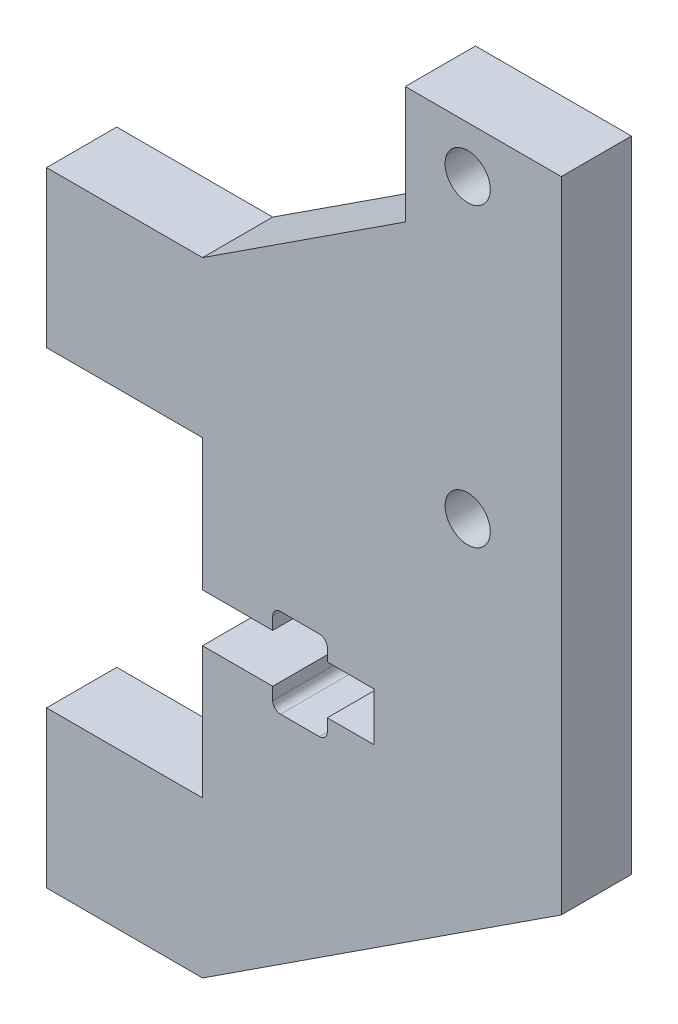
SolidWorks part; units mm, degrees
ref_plane "Front Plane" through (0, 0, 0) normal (0, 0, 1) x (1, 0, 0)
ref_plane "Top Plane" through (0, 0, 0) normal (0, 1, 0) x (1, 0, 0)
ref_plane "Right Plane" through (0, 0, 0) normal (1, 0, 0) x (0, 0, -1)
sketch "Sketch1" plane through (0, 0, 0) normal (0, 0, 1) x (1, 0, 0)
  line L0 (13, 3.4783) -> (0, -5)
  line L1 (0, -5) -> (-10, -5)
  line L2 (-10, -5) -> (-10, -15)
  line L3 (-10, -15) -> (0, -15)
  line L4 (0, -15) -> (0, -35)
  line L5 (0, -35) -> (-10, -35)
  line L6 (-10, -35) -> (-10, -45)
  line L7 (-10, -45) -> (0, -45)
  line L10 (0, -45) -> (23, -30)
  line L11 (23, -30) -> (23, 11)
  line L12 (23, 11) -> (13, 11)
  line L13 (13, 11) -> (13, 3.4783)
  line L15 (0, -5) -> (0, -45) construction
  line L16 (-10, -10) -> (0, -10) construction
  line L17 (-10, -40) -> (0, -40) construction
  line L18 (-10, -15) -> (-10, -35) construction
  line L19 (-10, -25) -> (0, -25) construction
  dimension "D1" = 10
  dimension "D2" = 10
  dimension "D3" = 10
  dimension "D4" = 10
  dimension "D5" = 15
  dimension "D8" = 10
  dimension "D10" = 13
  dimension "D6" = 15
  dimension "D7" = 16
extrude "Boss-Extrude1" add sketch "Sketch1" along normal blind 4.5
sketch "Sketch2" plane through (0, 0, 4.5) normal (0, 0, 1) x (1, 0, 0)
  line L0 (0, -25) -> (23, -25) construction
  line L1 (0, -15) -> (0, -35) construction
  line L3 (11, -26.55) -> (11, -23.45) construction
  line L4 (11, -23.45) -> (0, -23.45) construction
  line L5 (0, -26.55) -> (0, -23.45)
  line L6 (0, -23.45) -> (4.5, -23.45)
  line L7 (4.5, -23.45) -> (4.5, -22.65)
  line L8 (5, -22.15) -> (7.5, -22.15)
  line L9 (8, -22.65) -> (8, -23.45)
  line L10 (8, -23.45) -> (11, -23.45)
  line L11 (11, -23.45) -> (11, -26.55)
  line L12 (11, -26.55) -> (0, -26.55) construction
  line L13 (8, -26.55) -> (11, -26.55)
  line L14 (8, -27.35) -> (8, -26.55)
  line L15 (5, -27.85) -> (7.5, -27.85)
  line L16 (4.5, -26.55) -> (4.5, -27.35)
  line L17 (0, -26.55) -> (4.5, -26.55)
  line L18 (23, -30) -> (23, 11) construction
  arc A0 (7.5, -22.15) -> (8, -22.65) centre (7.5, -22.65) cw
  arc A1 (4.5, -22.65) -> (5, -22.15) centre (5, -22.65) cw
  arc A2 (4.5, -27.35) -> (5, -27.85) centre (5, -27.35) ccw
  arc A3 (7.5, -27.85) -> (8, -27.35) centre (7.5, -27.35) ccw
  point P15 (8, -22.15)
  point P18 (4.5, -22.15)
  point P27 (11, -25)
  point P29 (4.5, -27.85)
  point P30 (8, -27.85)
  dimension "D6" = 0.5
  dimension "D1" = 11
  dimension "D2" = 1.55
  dimension "D3" = 8
  dimension "D4" = 3.5
  dimension "D5" = 2.85
extrude "screw-cutout" cut sketch "Sketch2" against normal through all
sketch "Sketch3" plane through (0, 0, 4.5) normal (0, 0, 1) x (1, 0, 0)
  line L0 (17, 55) -> (17, -45) construction
  line L3 (13, 11) -> (13, 3.4783) construction
  line L5 (-10, -45) -> (0, -45) construction
  line L10 (11, -26.55) -> (11, -23.45) construction
  circle A1 centre (17, 8) radius 1.45
  circle A5 centre (17, -11) radius 1.45
  point P8 (11, -25)
  dimension "D4" = 2.9
  dimension "D11" = 2.9
  dimension "D6" = 4
  dimension "D12" = 19
  dimension "D2" = 14
extrude "Cut-Extrude2" cut sketch "Sketch3" against normal through all
sketch "Sketch4" [suppressed] plane through (0, 0, 4.5) normal (0, 0, 1) x (1, 0, 0)
  line L0 (17, -11) -> (17, 8) construction
  line L1 (17, -1.5) -> (13, -1.5) construction
  line L2 (13, 11) -> (13, 3.4783) construction
  line L4 (15, 2.5) -> (13, 2.5)
  line L5 (15, 2.5) -> (15, -5.5)
  line L6 (15, -5.5) -> (13, -5.5)
  line L7 (13, 2.5) -> (13, -5.5)
  line L8 (15, 2.5) -> (13, -5.5) construction
  line L9 (15, -5.5) -> (13, 2.5) construction
  circle A1 centre (17, 8) radius 1.55 construction
  circle A3 centre (17, -11) radius 1.55 construction
  point P11 (14, -1.5)
  dimension "D1" = 8
  dimension "D2" = 2
  dimension "D3" = 3
equation "\"X-ROD-SPACING\"=45"
equation "\"Y-ROD-SPACING\"=75"
equation "\"Z-ROD-SPACING\"=17.5"
equation "\"Y-BED-OFFSET\"=2"
equation "\"Y-BED-ROD-INSET\"=3.5"
equation "\"T-SLOT-NUT-FILLET-RADIUS\"=0.5"
equation "\"T-SLOT-SCREW-SHAFT-RADIUS\"=1.55"
equation "\"T-SLOT-SCREW-SHAFT-CUTOUT-LENGTH\"=11.0"
equation "\"T-SLOT-NUT-DEPTH\"=3.5"
equation "\"T-SLOT-NUT-WIDTH\"=2.85"
equation "\"T-SLOT-NUT-END-DISTANCE\"=8"
equation "\"ACRYLIC-THICKNESS\"=10"
equation "\"ACRYLIC-THICKNESS2\"=4.5"
equation "\"ACRYLIC-TAB-CUTOUT-SIZE\"=\"ACRYLIC-THICKNESS\"+\"ACRYLIC-TAB-TOLERANCE\"*2"
equation "\"ACRYLIC-TAB-WIDTH\"=\"ACRYLIC-THICKNESS\""
equation "\"ACRYLIC-M3-HOLE\"=2.9"
equation "\"SMOOTHROD-CAP-SCREW-DISTANCE\"=20"
equation "\"FRAME-WIDTH-INNER\"=370"
equation "\"NEMA17-HOLE-SPACING\"=31"
equation "\"NEMA17-CENTRAL-CUTOUT\"=22.5"
equation "\"Z-BRACKET-REACH\"=55"
equation "\"Z-ROD-INSET\"=16"
equation "\"TOP-BRACKET-SPACING\"=40"
equation "\"SMOOTHROD-X-LENGTH\"=350"
equation "\"SMOOTHROD-Y-LENGTH\"=350"
equation "\"SMOOTHROD-Z-LENGTH\"=350"
equation "\"SMOOTHROD-TIGHTENING-HEADROOM\"=.25"
equation "\"LEADSCREW-Z-LENGTH\"=300"
equation "\"SCREW-LENGTH-FRAME\"=\"ACRYLIC-THICKNESS\" + 10"
equation "\"SCREW-HEAD-RADIUS\"=6"
equation "\"PRINTED-X-SMOOTHROD-DIAMETER\"=8.4"
equation "\"PRINTED-X-SMOOTHROD-CUTOUT\"=10"
equation "\"PRINTED-X-BASE-HEIGHT\"=10"
equation "\"PRINTED-LM8UU-CUTOUT-SIZE\"=15.5"
equation "\"PRINTED-LM8UU-CUTOUT-LENGTH\"=24.5"
equation "\"PRINTED-X-IDLER-HEIGHT\"=16"
equation "\"PSU-MOUNTING-WIDTH\"=95"
equation "\"PSU-MOUNTING-HEIGHT\"=177"
equation "\"Y-BELT-TO-ROD-DISTANCE\"=20"
equation "\"SPOOL-HOLDER-ROD-SPACING\"=150"
equation "\"D1@Sketch1\"=\"ACRYLIC-TAB-WIDTH\""
equation "\"D2@Sketch1\"=\"ACRYLIC-TAB-WIDTH\""
equation "\"D3@Sketch1\"=\"ACRYLIC-THICKNESS\""
equation "\"D4@Sketch1\"=\"ACRYLIC-THICKNESS\""
equation "\"D1@Boss-Extrude1\"=\"ACRYLIC-THICKNESS2\""
equation "\"D1@Sketch2\"=\"T-SLOT-SCREW-SHAFT-CUTOUT-LENGTH\""
equation "\"D2@Sketch2\"=\"T-SLOT-SCREW-SHAFT-RADIUS\""
equation "\"D3@Sketch2\"=\"T-SLOT-NUT-END-DISTANCE\""
equation "\"D4@Sketch2\"=\"T-SLOT-NUT-DEPTH\""
equation "\"D5@Sketch2\"=\"T-SLOT-NUT-WIDTH\""
equation "\"D6@Sketch2\"=\"T-SLOT-NUT-FILLET-RADIUS\""
equation "\"D4@Sketch3\"=\"ACRYLIC-M3-HOLE\""
equation "\"D11@Sketch3\"=\"ACRYLIC-M3-HOLE\""
equation "\"Y-BED-SCREW-SPACING\"=209"
equation "\"Y-BED-SCREW-CUTOUT-SLOT-HEIGHT\"=2"
equation "\"ACRYLIC-TAB-TOLERANCE\"=-.05"
equation "\"SCREW-LENGTH-MOTOR\"=\"ACRYLIC-THICKNESS\" + 5"
equation "\"SCREW-LENGTH-EXTRUDER\"=28"
equation "\"PRINTED-M3-HOLE\"=3.5"
equation "\"ACRYLIC-X-CARRIAGE-WIDTH\"=55"
equation "\"ACRYLIC-X-CARRIAGE-HEIGHT\"=75"
equation "\"ACRYLIC-X-CARRIAGE-LM8UU-CUTOUT-WIDTH\"=24.25"
equation "\"ACRYLIC-X-CARRIAGE-LM8UU-CUTOUT-HEIGHT\"=11.0"
equation "\"ACRYLIC-X-CARRIAGE-SCREW-SPACING-X\"=15"
equation "\"ACRYLIC-X-CARRIAGE-SCREW-SPACING-Y\"=33"
equation "\"ACRYLIC-X-CARRIAGE-CENTER-TAB-SPACING\"=14"
equation "\"ACRYLIC-X-CARRIAGE-EXTRUDER-OFFSET\"=26"
equation "\"ACRYLIC-X-CARRIAGE-EXTRUDER-ANGLE\"=90"
equation "\"ACRYLIC-X-CARRIAGE-EXTRUDER-SHELF-DEPTH\"=\"ACRYLIC-X-CARRIAGE-EXTRUDER-OFFSET\" + 28"
equation "\"ACRYLIC-X-CARRIAGE-EXTRUDER-BRACE-SPACING\"=23"
equation "\"ACRYLIC-X-CARRIAGE-EXTRUDER-BRACE-TAB-OFFSET\"=20"
equation "\"ACRYLIC-X-CARRIAGE-EXTRUDER-BRACE-HEIGHT\"=35"
equation "\"ACRYLIC-X-CARRIAGE-EXTRUDER-BRACE-SCREW-SPACING\"=22"
equation "\"ACRYLIC-X-CARRIAGE-DUAL-WIDTH-MULTIPLIER\"=1.65"
equation "\"ACRYLIC-X-CARRIAGE-DUAL-HOTEND-SPACING\"=42"
equation "\"ACRYLIC-X-CARRIAGE-DUAL-WIDTH\"=75"
equation "\"ACRYLIC-X-CARRIAGE-DUAL-HOTEND-SEPARATION\"=36"
equation "\"ACRYLIC-X-CARRIAGE-DUAL-MOUNT-PLATE-DEPTH\"=75"
equation "\"ACRYLIC-X-CARRIAGE-DUAL-MOUNT-BRACE-WIDTH\"=33"
equation "\"ACRYLIC-X-CARRIAGE-DUAL-MOUNT-SCREW-WIDTH\"=40"
equation "\"BLOWER-FAN-WIDTH\"=15"
